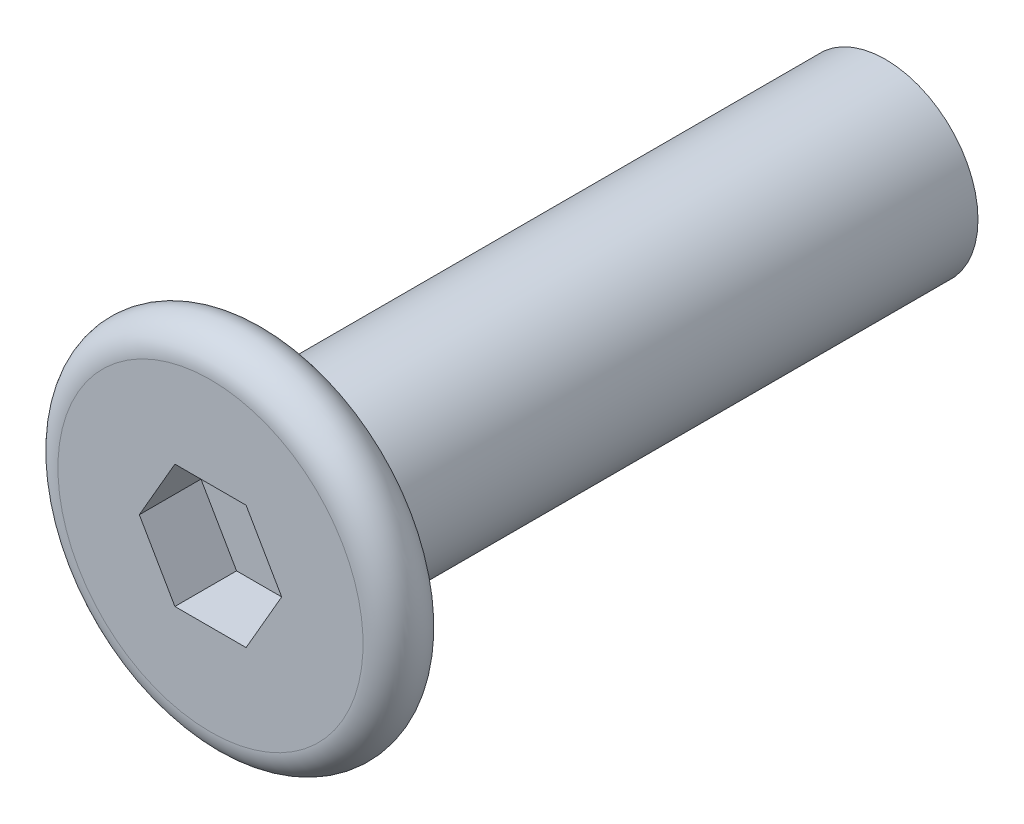
SolidWorks part; units mm, degrees
material "AISI 304"
ref_plane "前视基准面" through (0, 0, 0) normal (0, 0, 1) x (1, 0, 0)
ref_plane "上视基准面" through (0, 0, 0) normal (0, 1, 0) x (1, 0, 0)
ref_plane "右视基准面" through (0, 0, 0) normal (1, 0, 0) x (0, 0, -1)
sketch "草图1" plane through (0, 0, 0) normal (1, 0, 0) x (0, 0, -1)
  line L0 (0, 0) -> (0, 2.95)
  line L1 (0, 2.95) -> (0.95, 2.95)
  line L2 (0.95, 2.95) -> (0.95, 1.5)
  line L3 (0.95, 1.5) -> (10.95, 1.5)
  line L4 (10.95, 1.5) -> (10.95, 0)
  line L5 (10.95, 0) -> (0, 0) construction
  line L6 (0, 0) -> (10.95, 0)
  dimension "螺纹大径" = 3
  dimension "螺纹长度" = 10
  dimension "头部厚度" = 0.95
  dimension "头部直径" = 5.9
revolve "旋转1" add sketch "草图1" angle 360 about L5
cosmetic thread "装饰螺纹线1" parameters "D2"=1
fillet "圆角1" 2 edges at (0, 2.95, 0) (0, 2.95, -0.95) type full round first side face at (0, 2.95, 0) second side face at (0, 2.95, -0.95) middle face at (0, 2.95, 0)
sketch "草图2" plane through (0, 0, 0) normal (0, 0, 1) x (1, 0, 0)
  line L1 (0.5774, 1) -> (-0.5774, 1)
  line L2 (-0.5774, 1) -> (-1.1547, 0)
  line L3 (-1.1547, 0) -> (-0.5774, -1)
  line L4 (-0.5774, -1) -> (0.5774, -1)
  line L5 (0.5774, -1) -> (1.1547, 0)
  line L6 (1.1547, 0) -> (0.5774, 1)
  circle A0 centre (0, 0) radius 1 construction
  dimension "D1" = 2
extrude "切除-拉伸1" cut sketch "草图2" against normal blind 1
